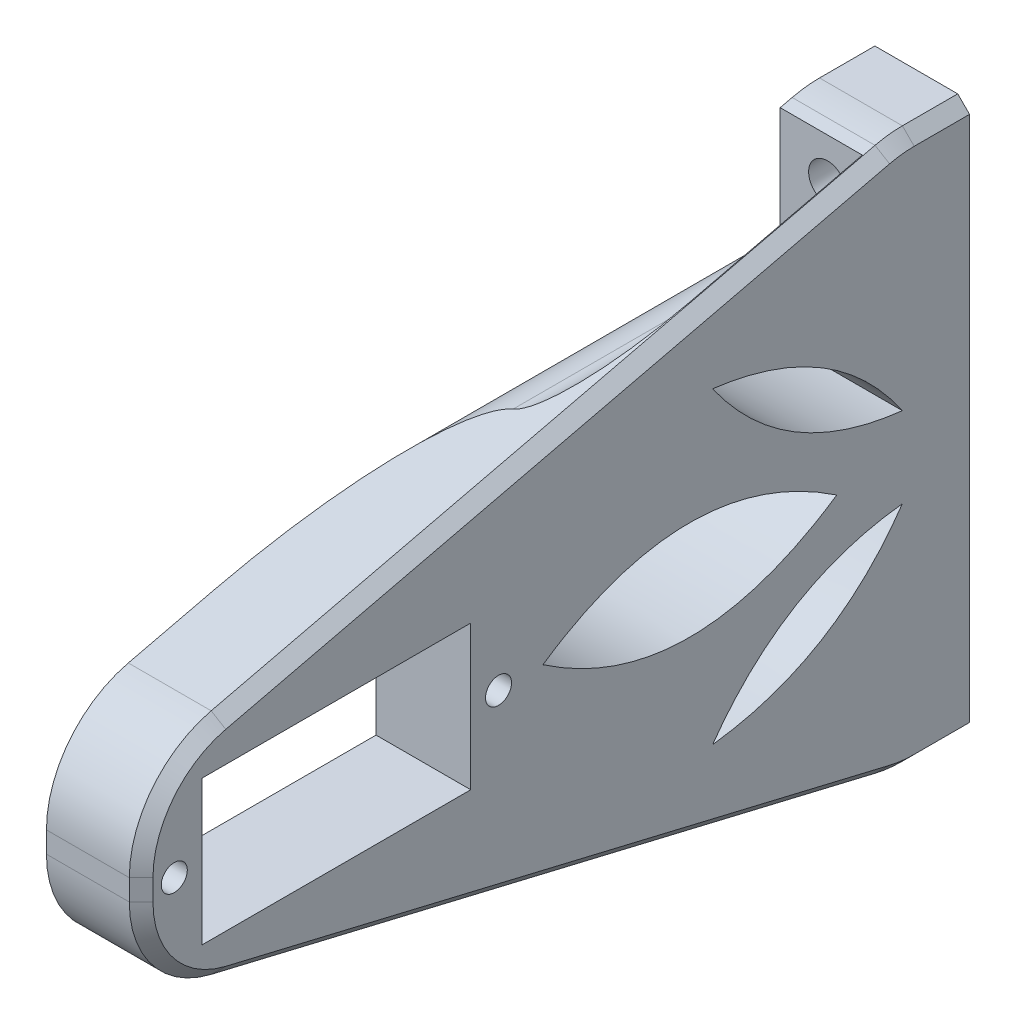
SolidWorks part; units mm, degrees
ref_plane "Front Plane" through (0, 0, 0) normal (0, 0, 1) x (1, 0, 0)
ref_plane "Top Plane" through (0, 0, 0) normal (0, 1, 0) x (1, 0, 0)
ref_plane "Right Plane" through (0, 0, 0) normal (1, 0, 0) x (0, 0, -1)
sketch "Sketch1" plane through (0, 0, 0) normal (0, 0, 1) x (1, 0, 0)
  line L0 (34.4583, 19.25) -> (38.4593, 19.25) construction
  line L1 (38.4593, 19.25) -> (38.4593, -19.25) construction
  line L2 (38.4593, -19.25) -> (38.4593, -23.25) construction
  line L3 (34.4583, 19.25) -> (34.4583, 23.25) construction
  line L4 (34.4583, 23.25) -> (30.4583, 23.25) construction
  line L6 (30.4583, 23.25) -> (38.4593, 23.25)
  line L7 (30.4583, 23.25) -> (30.4583, -23.25)
  line L8 (30.4583, -23.25) -> (38.4593, -23.25)
  line L9 (38.4593, 23.25) -> (38.4593, -23.25)
  dimension "D1" = 4
  dimension "D2" = 38.5
extrude "Boss-Extrude1" add sketch "Sketch1" along normal blind 70
sketch "Sketch2" plane through (38.4593, 0, 0) normal (1, 0, 0) x (0, 0, -1)
  line L0 (0, -23.25) -> (-4.676, -23.25)
  line L1 (-70, -23.25) -> (0, -23.25) construction
  line L2 (-70, 0) -> (-70, -8)
  line L3 (-70, -23.25) -> (-70, 23.25) construction
  line L4 (-70, -8) -> (-6.9887, -22.9789)
  line L5 (-70, 0) -> (-70, 8)
  line L6 (0, 23.25) -> (-4.676, 23.25)
  line L7 (-70, 23.25) -> (0, 23.25) construction
  line L8 (-6.9887, 22.9789) -> (-70, 8)
  line L9 (0, -23.25) -> (0, -41.3542)
  line L10 (0, 53) -> (0, -53) construction
  line L11 (0, -41.3542) -> (-74.8247, -41.3542)
  line L12 (-74.8247, -41.3542) -> (-74.8247, 33.4627)
  line L13 (-74.8247, 33.4627) -> (0, 33.4627)
  line L14 (0, 33.4627) -> (0, 23.25)
  line L15 (0, 0) -> (-36.0482, 0) construction
  line L16 (0, 0) -> (-21.7142, 13.0211) construction
  arc A0 (-4.676, 23.25) -> (-6.9887, 22.9789) centre (-4.676, 13.25) ccw
  arc A1 (-4.676, -23.25) -> (-6.9887, -22.9789) centre (-4.676, -13.25) cw
  spline S0 degree 2 poles (-36.0482, 0) (-23.7136, -8.3881) (-11.2189, 0) knots 0 0 0 1 1 1
  spline S1 degree 2 poles (-5.6804, 3.4063) (-15.7249, 4.5117) (-21.7142, 13.0211) knots 0 0 0 1 1 1
  spline S2 degree 2 poles (-36.0482, 0) (-23.7136, 8.3881) (-11.2189, 0) knots 0 0 0 1 1 1
  spline S3 degree 2 poles (-5.6804, 3.4063) (-11.3868, 11.746) (-21.7142, 13.0211) knots 0 0 0 1 1 1
  spline S4 degree 2 poles (-5.6804, -3.4063) (-15.7249, -4.5117) (-21.7142, -13.0211) knots 0 0 0 1 1 1
  spline S5 degree 2 poles (-5.6804, -3.4063) (-11.3868, -11.746) (-21.7142, -13.0211) knots 0 0 0 1 1 1
  point P37 (-5.8482, 23.25)
  point P40 (-5.8482, -23.25)
  dimension "D1" = 10
extrude "Cut-Extrude1" cut sketch "Sketch2" against normal blind 70
sketch "Sketch3" plane through (30.4583, 0, 0) normal (-1, 0, 0) x (0, 0, 1)
  line L0 (70, 8) -> (70, -8) construction
  line L1 (70, -6.1) -> (37, -6.1) construction
  line L2 (70, -6.1) -> (70, 6.1) construction
  line L3 (70, 6.1) -> (37, 6.1) construction
  line L4 (37, -6.1) -> (37, 6.1) construction
  line L5 (70, 8) -> (70, -8) construction
  line L6 (70, 0) -> (37, 0) construction
  line L7 (53.5, 0) -> (53.5, 6.1) construction
  line L8 (53.5, 6.1) -> (42.15, 6.1)
  line L9 (42.15, 6.1) -> (42.15, -6.1)
  line L10 (42.15, -6.1) -> (64.85, -6.1)
  line L11 (64.85, -6.1) -> (64.85, 6.1)
  line L12 (64.85, 6.1) -> (53.5, 6.1)
  line L13 (64.85, 0) -> (67.2, 0) construction
  circle A0 centre (67.2, 0) radius 1.1
  circle A1 centre (39.8, 0) radius 1.1
  point P6 (70, 0)
  point P11 (70, 0)
  dimension "D1" = 12.2
  dimension "D2" = 33
extrude "Cut-Extrude2" cut sketch "Sketch3" against normal blind 70 contours L8 L9 L10 L11 L12 | A1 | A0
fillet "Fillet1" radius 9 2 edges at (34.4588, 8, 70) (34.4588, -8, 70)
sketch "Sketch4" plane through (0, 0, 70) normal (0, 0, 1) x (1, 0, 0)
  line L0 (34.4588, 0) -> (34.4588, -19.25) construction
  line L1 (30.4583, 0) -> (38.4593, 0) construction
  line L2 (38.4593, 0) -> (34.4588, 0) construction
  line L4 (30.4583, 9.6447) -> (30.4583, 22.9789) construction
  line L5 (30.4583, 22.1882) -> (30.4583, 16.3118)
  line L6 (30.4583, 16.3118) -> (34.4588, 16.3118)
  line L7 (34.4588, -16.3118) -> (30.4583, -16.3118)
  line L8 (30.4583, -22.9789) -> (30.4583, -9.6447) construction
  line L9 (30.4583, -16.3118) -> (30.4583, -22.1882)
  line L11 (37.397, -19.25) -> (37.397, -23.25)
  line L12 (30.4583, -23.25) -> (38.4593, -23.25) construction
  line L13 (37.397, 19.25) -> (37.397, 23.25)
  line L14 (30.4583, 23.25) -> (38.4593, 23.25) construction
  line L15 (30.4583, 22.1882) -> (30.4583, 24.5006)
  line L16 (30.4583, 24.5006) -> (37.397, 23.25)
  line L17 (37.397, -23.25) -> (30.4583, -24.7382)
  line L18 (30.4583, -24.7382) -> (30.4583, -22.1882)
  arc A0 (37.397, -19.25) -> (34.4588, -16.3118) centre (34.4588, -19.25) ccw
  arc A1 (37.397, 19.25) -> (34.4588, 16.3118) centre (34.4588, 19.25) cw
extrude "Cut-Extrude3" cut sketch "Sketch4" against normal blind 62 contours A0 L7 L9 | A1 L5 L6 region at (33.7256, 20.2168, 70) region at (33.7103, -20.2801, 70)
sketch "Sketch5" plane through (0, 0, 8) normal (0, 0, 1) x (1, 0, 0)
  circle A0 centre (34.4588, 19.25) radius 1.6
  circle A1 centre (34.4588, -19.25) radius 1.6
extrude "Cut-Extrude4" cut sketch "Sketch5" against normal blind 62
fillet "Fillet2" radius 5 2 edges at (30.4583, -16.3118, 21.5175) (30.4583, 16.3118, 21.5175)
chamfer "Chamfer1" distance 1 angle 45 9 edges at (38.4593, -23.25, 2.338) (38.4593, -23.182, 5.8403) (38.4593, 23.25, 2.338) (38.4593, -16.3118, 35.0351) (38.4593, 23.182, 5.8403) (38.4593, -6.4684, 68.0616) (38.4593, 0, 70) (38.4593, 6.4684, 68.0616) (38.4593, 16.3118, 35.0351)
